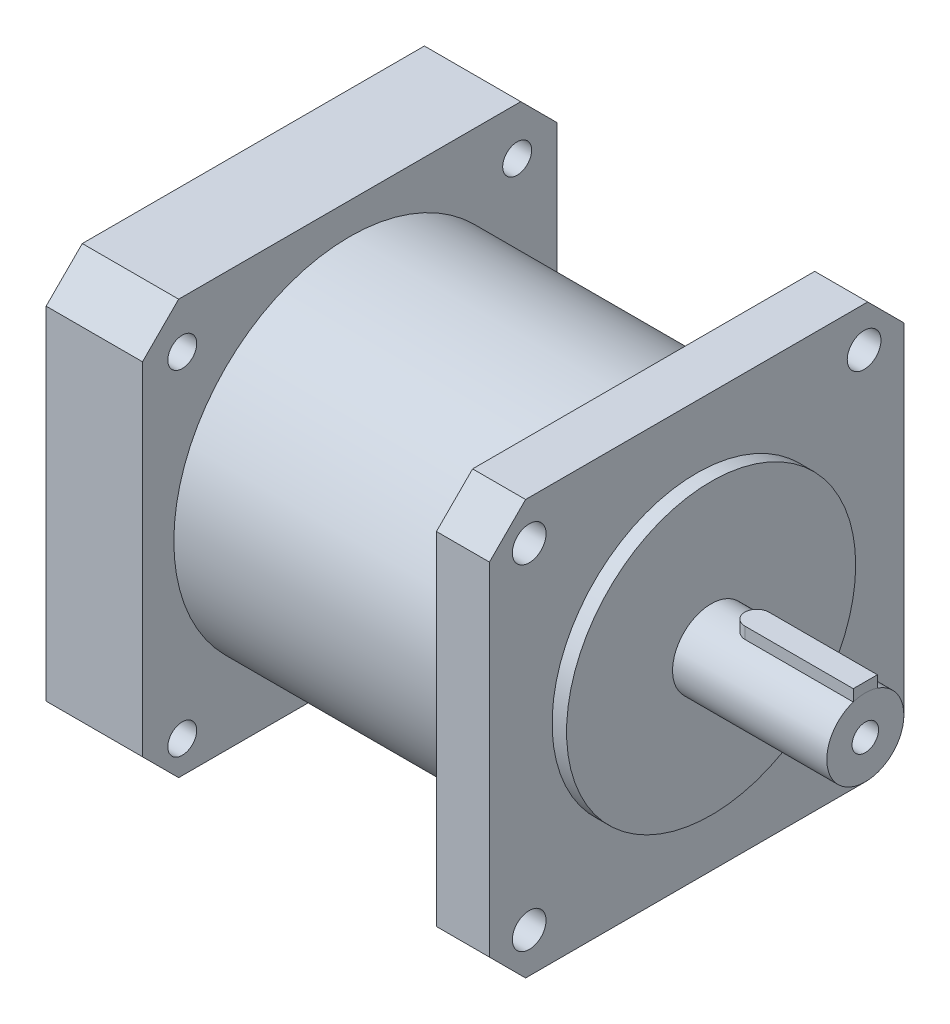
SolidWorks part; units mm, degrees
other "Markup1"
sketch "Sketch15" plane through (127, -43, -43) normal (0.9967, -0.0807, -0.0069) x (-0.0318, -0.3117, -0.9497)
material "gearbox"
ref_plane "Front Plane" through (0, 0, 0) normal (0, 0, 1) x (1, 0, 0)
ref_plane "Top Plane" through (0, 0, 0) normal (0, 1, 0) x (1, 0, 0)
ref_plane "Right Plane" through (0, 0, 0) normal (1, 0, 0) x (0, 0, -1)
sketch "Sketch1" plane through (0, 0, 0) normal (1, 0, 0) x (0, 0, -1)
  line L1 (-43, 43) -> (43, 43)
  line L2 (-43, 43) -> (-43, -43)
  line L3 (-43, -43) -> (43, -43)
  line L4 (43, 43) -> (43, -43)
  line L5 (-43, 43) -> (43, -43) construction
  line L6 (-43, -43) -> (43, 43) construction
  circle A0 centre (0, 0) radius 36.5
  dimension "D1" = 86
  dimension "D3" = 73
  dimension "D2" = 86
extrude "Boss-Extrude1" add sketch "Sketch1" along normal blind 81 contours A0
extrude "Boss-Extrude2" add sketch "Sketch1<3>" along normal blind 20
sketch "Sketch1<3>" plane through (0, 0, 0) normal (1, 0, 0) x (0, 0, -1) same geometry as "Sketch1"
sketch "Sketch2" plane through (0, 0, 0) normal (-1, 0, 0) x (0, 0, 1)
  line L0 (-2.5, 9.3) -> (2.5, 9.3)
  line L1 (-2.5, 9.3) -> (-2.5, 6.5383)
  line L2 (2.5, 9.3) -> (2.5, 6.5383)
  arc A0 (-2.5, 6.5383) -> (2.5, 6.5383) centre (0, 0) ccw
  point P5 (0, 9.3)
  point P6 (0, -7)
  dimension "D1" = 14
  dimension "D2" = 5
  dimension "D3" = 16.3
extrude "Cut-Extrude1" cut sketch "Sketch2" against normal blind 37
sketch "Sketch4" plane through (81, 0, 0) normal (1, 0, 0) x (0, 0, -1)
  line L1 (-43, 43) -> (43, 43)
  line L2 (-43, 43) -> (-43, -43)
  line L3 (-43, -43) -> (43, -43)
  line L4 (43, 43) -> (43, -43)
  line L5 (-43, 43) -> (43, -43) construction
  line L6 (-43, -43) -> (43, 43) construction
  point P0 (0, 0)
extrude "Boss-Extrude3" add sketch "Sketch4" along normal blind 11
sketch "Sketch5" plane through (92, 0, 0) normal (1, 0, 0) x (0, 0, -1)
  circle A0 centre (0, 0) radius 30
  dimension "D1" = 60
extrude "Boss-Extrude4" add sketch "Sketch5" along normal blind 3
sketch "Sketch6" plane through (95, 0, 0) normal (1, 0, 0) x (0, 0, -1)
  circle A0 centre (0, 0) radius 8
  point P7 (0, -8)
  dimension "D1" = 16
extrude "Boss-Extrude6" add sketch "Sketch6" along normal blind 32
sketch "Sketch8" plane through (127, 0, 0) normal (1, 0, 0) x (0, 0, -1)
  line L0 (-2.5, 10) -> (2.5, 10)
  line L1 (-2.5, 10) -> (-2.5, 7.5993)
  line L2 (2.5, 10) -> (2.5, 7.5993)
  circle A0 centre (0, 0) radius 8 construction
  arc A1 (-2.5, 7.5993) -> (2.5, 7.5993) centre (0, 0) cw
  point P0 (0, 10)
  point P5 (0, 10)
  circle M2 centre (0, 0) radius 8
  dimension "D1" = 10
  dimension "D2" = 5
extrude "Boss-Extrude8" add sketch "Sketch8" against normal blind 32 separate body contours L2 L0 L1 M2 region at (127, 8.9306, 0)
sketch "Sketch10" plane through (0, 10, 0) normal (0, 1, 0) x (1, 0, 0)
  line L0 (127, -2.5) -> (127, 2.5) construction
  line L1 (95, 2.5) -> (127, 2.5) construction
  line L2 (95, -2.5) -> (127, -2.5) construction
  line L3 (104.5, -2.5) -> (95, -2.5)
  line L4 (95, -2.5) -> (95, 2.5)
  line L5 (95, -30) -> (95, 30) construction
  line L6 (95, -2.5) -> (95, 2.5) construction
  line L7 (95, 2.5) -> (104.5, 2.5)
  arc A0 (104.5, 2.5) -> (104.5, -2.5) centre (104.5, 0) ccw
  point P0 (127, 0)
  point P1 (102, 0)
  point P4 (104.5, 0)
  dimension "D1" = 25
  dimension "D2" = 2.5
extrude "Cut-Extrude3" cut sketch "Sketch10" against normal up to surface (2.4007 mm away) up to face at (127, 0, -8)
chamfer "Chamfer1" distance 7.5 angle 45 8 edges at (10, -43, 43) (86.5, -43, 43) (86.5, -43, -43) (10, -43, -43) (10, 43, -43) (86.5, 43, -43) (86.5, 43, 43) (10, 43, 43)
sketch "Sketch13" plane through (92, 0, 0) normal (1, 0, 0) x (0, 0, -1)
  circle A0 centre (-34.75, -34.75) radius 3.5
  circle A1 centre (34.75, -34.75) radius 3.5
  circle A2 centre (34.75, 34.75) radius 3.5
  circle A3 centre (-34.75, 34.75) radius 3.5
  point P0 (-34.75, -34.75)
  point P1 (34.75, -34.75)
  point P3 (0, -34.75)
  dimension "D3" = 7
  dimension "D5" = 7
  dimension "D6" = 7
  dimension "D7" = 7
  dimension "D1" = 69.5
  dimension "D2" = 34.75
  dimension "D4" = 69.5
extrude "Cut-Extrude7" cut sketch "Sketch13" against normal blind 32
sketch "Sketch14" plane through (0, 0, 0) normal (-1, 0, 0) x (0, 0, 1)
  circle A0 centre (-34.75, -36.341) radius 3
  circle A1 centre (34.75, -36.341) radius 3
  circle A2 centre (34.75, 33.159) radius 3
  circle A3 centre (-34.75, 33.159) radius 3
  point P0 (-34.75, -36.341)
  point P2 (34.75, -36.341)
  dimension "D3" = 69.5
  dimension "D5" = 6
  dimension "D6" = 6
  dimension "D7" = 6
  dimension "D8" = 6
  dimension "D2" = 69.5
  dimension "D4" = 69.5
extrude "Cut-Extrude8" cut sketch "Sketch14" against normal blind 32
sketch "Sketch16" plane through (127, 0, 0) normal (1, 0, 0) x (0, 0, -1)
  circle A0 centre (0, 0) radius 2.75
  dimension "D1" = 5.5
extrude "Cut-Extrude9" cut sketch "Sketch16" against normal blind 15
